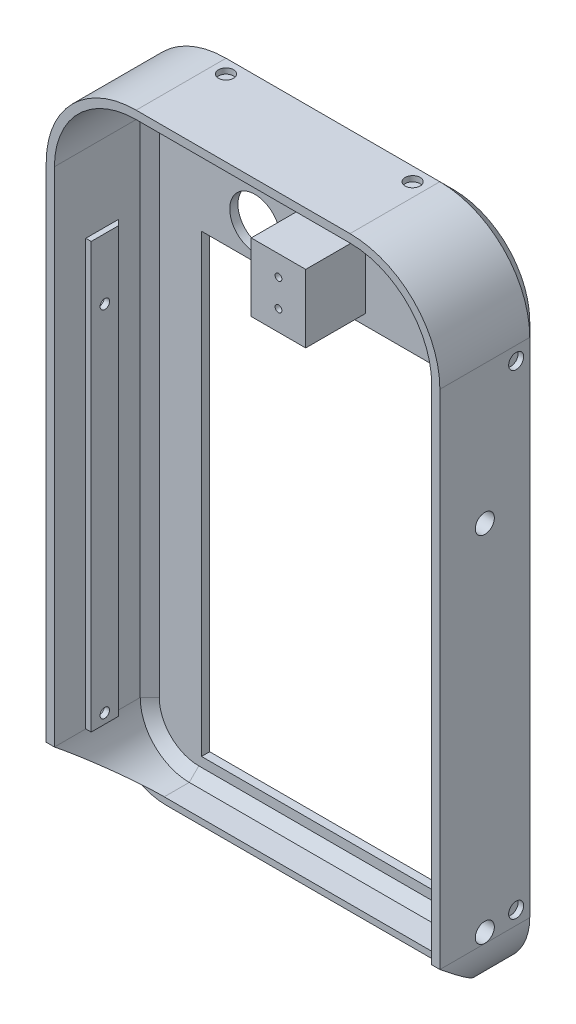
SolidWorks part; units mm, degrees
ref_plane "Plan de face" through (0, 0, 0) normal (0, 0, 1) x (1, 0, 0)
ref_plane "Plan de dessus" through (0, 0, 0) normal (0, 1, 0) x (1, 0, 0)
ref_plane "Plan de droite" through (0, 0, 0) normal (1, 0, 0) x (0, 0, -1)
sketch "Esquisse1" plane through (0, 0, 0) normal (0, 0, 1) x (1, 0, 0)
  line L1 (-12.2348, 13.2576) -> (7.7652, 13.2576)
  line L2 (-12.2348, 13.2576) -> (-12.2348, -11.7424)
  line L3 (-12.2348, -11.7424) -> (7.7652, -11.7424)
  line L4 (7.7652, 13.2576) -> (7.7652, -11.7424)
  dimension "D1" = 20
  dimension "D2" = 25
extrude "Boss.-Extru.1" add sketch "Esquisse1" along normal blind 22
sketch "Esquisse2" plane through (0, 0, 22) normal (0, 0, 1) x (1, 0, 0)
  line L0 (-12.2348, 0.7576) -> (7.7652, 0.7576) construction
  line L1 (-12.2348, 13.2576) -> (-12.2348, -11.7424) construction
  line L2 (7.7652, -11.7424) -> (7.7652, 13.2576) construction
  line L3 (-2.2348, 5.7576) -> (-2.2348, -4.2424) construction
  circle A0 centre (-2.2348, 5.7576) radius 1.25
  circle A1 centre (-2.2348, -4.2424) radius 1.25
  point P13 (-2.2348, 0.7576)
  point P14 (-2.2348, 0.7576)
  dimension "D2" = 2.5
  dimension "D1" = 10
extrude "Enlèv. mat.-Extru.1" cut sketch "Esquisse2" against normal blind 15
sketch "Esquisse3" plane through (0, 0, 0) normal (0, 0, -1) x (-1, 0, 0)
  line L1 (74.4938, -15.7424) -> (-70.0241, -15.7424)
  line L2 (74.4938, -15.7424) -> (74.4938, 45.7576)
  line L3 (74.4938, 45.7576) -> (-70.0241, 45.7576)
  line L4 (-70.0241, -15.7424) -> (-70.0241, 45.7576)
  line L5 (-7.7652, 13.2576) -> (12.2348, 13.2576) construction
  line L7 (12.2348, -11.7424) -> (-7.7652, -11.7424) construction
  line L8 (12.2348, 13.2576) -> (12.2348, -11.7424) construction
  line L9 (-7.7652, -11.7424) -> (-7.7652, 13.2576) construction
  dimension "D1" = 4
  dimension "D2" = 62.2589
  dimension "D3" = 62.2589
  dimension "D4" = 32.5
extrude "Wall" add sketch "Esquisse3" along normal blind 3
sketch "Esquisse4" plane through (0, 0, -3) normal (0, 0, -1) x (-1, 0, 0)
  line L1 (-70.0241, -15.7424) -> (74.4938, -15.7424) construction
  line L2 (12.2348, 13.2576) -> (12.2348, -11.7424) construction
  line L3 (-32.7652, 28.7576) -> (32.2348, 28.7576) construction
  line L4 (-32.7652, 39.2576) -> (32.2348, 39.2576)
  line L5 (-32.7652, 18.2576) -> (32.2348, 18.2576)
  line L7 (74.4938, -15.7424) -> (74.4938, 45.7576) construction
  circle A0 centre (32.8698, -3.4521) radius 9.25
  arc A1 (-32.7652, 39.2576) -> (-32.7652, 18.2576) centre (-32.7652, 28.7576) ccw
  arc A2 (32.2348, 18.2576) -> (32.2348, 39.2576) centre (32.2348, 28.7576) ccw
  point P8 (-0.2652, 28.7576)
  point P13 (1.2337, 22.3958)
  point P14 (-29.4209, 22.6205)
  point P17 (-32.7652, 17.5685)
  dimension "D1" = 18.5
  dimension "D7" = 10.5
  dimension "D2" = 20.635
  dimension "D3" = 12.2903
  dimension "D4" = 44.5
  dimension "D5" = 42.2589
  dimension "D6" = 65
extrude "Cameras" cut sketch "Esquisse4" against normal up to next
sketch "Esquisse9" plane through (0, 0, -3) normal (0, 0, -1) x (-1, 0, 0)
  line L0 (-48.0241, -182.7424) -> (52.4938, -182.7424)
  line L1 (-70.0241, -15.7424) -> (-48.0241, -15.7424)
  line L2 (-70.0241, -15.7424) -> (-70.0241, -192.7424)
  line L4 (-48.0241, -15.7424) -> (-48.0241, -182.7424)
  line L5 (74.4938, -15.7424) -> (52.4938, -15.7424)
  line L6 (74.4938, -15.7424) -> (74.4938, -192.7424)
  line L8 (52.4938, -15.7424) -> (52.4938, -182.7424)
  line L9 (-70.0241, -192.7424) -> (74.4938, -192.7424)
  dimension "D1" = 22
  dimension "D2" = 22
  dimension "D3" = 167
  dimension "D4" = 10
extrude "Screen" add sketch "Esquisse9" against normal up to surface (3 mm away) up to face at (-42.1198, -3.4521, 0)
sketch "Esquisse5" plane through (0, 0, 0) normal (0, 0, 1) x (1, 0, 0)
  line L2 (-74.4938, -192.7424) -> (-74.4938, 45.7576)
  line L7 (70.0241, 45.7576) -> (70.0241, -192.7424)
  line L10 (-74.4938, 45.7576) -> (70.0241, 45.7576) construction
  line L11 (-74.4938, 45.7576) -> (70.0241, 45.7576)
  line L12 (-71.4938, -189.7424) -> (-71.4938, 42.7576)
  line L13 (-71.4938, 42.7576) -> (67.0241, 42.7576)
  line L14 (67.0241, 42.7576) -> (67.0241, -189.7424)
  line L15 (-2.2348, 42.7576) -> (-2.2348, 45.7576) construction
  line L18 (-74.4938, -192.7424) -> (70.0241, -192.7424) construction
  line L19 (-71.4938, -189.7424) -> (67.0241, -189.7424)
  line L20 (-2.2348, -189.7424) -> (-2.2348, -192.7424) construction
  line L21 (-71.4938, -189.7424) -> (-74.4938, -189.7424) construction
  point P17 (-71.4938, -189.7424)
  point P18 (61.5641, -189.7424)
  line M11 (-74.4938, 45.7576) -> (-74.4938, -192.7424)
  line M13 (70.0241, -192.7424) -> (70.0241, 45.7576)
  line M14 (70.0241, 45.7576) -> (-74.4938, 45.7576)
  line M32 (-74.4938, -192.7424) -> (70.0241, -192.7424)
  dimension "D1" = 3
extrude "Boss.-Extru.3" add sketch "Esquisse5" along normal blind 35 contours L19 L12 L13 L14 M14 M11 M32 M13 region at (-71.7051, -73.4924, 0)
fillet "Congé1" radius 30 2 edges at (-71.4938, 42.7576, 17.5) (67.0241, 42.7576, 17.5)
fillet "Congé2" radius 33 2 edges at (-74.4938, 45.7576, 16) (70.0241, 45.7576, 16)
fillet "Congé3" radius 18 2 edges at (-71.4938, -189.7424, 17.5) (67.0241, -189.7424, 17.5)
fillet "Congé4" radius 21 2 edges at (-74.4938, -192.7424, 16) (70.0241, -192.7424, 16)
chamfer "Chanfrein1" distance 5 angle 45 8 edges at (-74.4938, -79.4924, -3) (-64.8283, 36.0921, -3) (-2.2348, 45.7576, -3) (70.0241, -79.4924, -3) (60.3586, 36.0921, -3) (-68.343, -186.5917, -3) (-2.2348, -192.7424, -3) (63.8733, -186.5917, -3)
chamfer "Chanfrein2" distance 3.5 angle 45 8 edges at (-71.4938, -79.4924, 0) (-62.707, 33.9708, 0) (67.0241, -79.4924, 0) (-2.2348, 42.7576, 0) (58.2373, 33.9708, 0) (-66.2217, -184.4703, 0) (-2.2348, -189.7424, 0) (61.752, -184.4703, 0)
sketch "Esquisse16" plane through (70.0241, 0, 0) normal (1, 0, 0) x (0, 0, -1)
  line L0 (-35, -171.7424) -> (-12, -190.286)
  line L1 (-12, -190.286) -> (-12, -192.7424)
  line L2 (-12, -192.7424) -> (-35, -192.7424)
  line L3 (-35, -192.7424) -> (-35, -171.7424)
  line L4 (-2, -192.7424) -> (-2, -171.7424) construction
  line L5 (-35, -192.7424) -> (-2, -192.7424) construction
  dimension "D1" = 10
extrude "Enlèv. mat.-Extru.9" cut sketch "Esquisse16" against normal through all
ref_plane "Plan1" through (0, 0, 13.5) normal (0, 0, 1) x (1, 0, 0)
sketch "Esquisse11" plane through (0, 0, 13.5) normal (0, 0, 1) x (1, 0, 0)
  line L0 (67.0241, 12.7576) -> (67.0241, -171.7424) construction
  line L1 (67.0241, -171.7424) -> (59.5641, -171.7424)
  line L2 (67.0241, -171.7424) -> (67.0241, -15.7424)
  line L3 (67.0241, -15.7424) -> (59.5641, -15.7424)
  line L4 (59.5641, -171.7424) -> (59.5641, -15.7424)
  line L5 (-69.4938, -171.7424) -> (-71.4938, -171.7424)
  line L6 (-69.4938, -171.7424) -> (-69.4938, -15.7424)
  line L7 (-69.4938, -15.7424) -> (-71.4938, -15.7424)
  line L8 (-71.4938, -171.7424) -> (-71.4938, -15.7424)
  line L10 (-71.4938, -171.7424) -> (-71.4938, 12.7576) construction
  point P10 (61.5641, -180.8212)
  point P16 (0, 0)
  dimension "D1" = 7.46
  dimension "D2" = 2
extrude "Boss.-Extru.5" add sketch "Esquisse11" along normal blind 10
chamfer "Chanfrein3" distance 2 angle 45 1 edges at (-71.4938, -93.7424, 13.5)
chamfer "Chanfrein4" distance 7.46 angle 45 1 edges at (67.0241, -93.7424, 13.5)
sketch "Esquisse12" plane through (59.5641, 0, 0) normal (-1, 0, 0) x (0, 0, 1)
  line L0 (23.5, -15.7424) -> (13.5, -15.7424) construction
  circle A0 centre (18.5, -38.1314) radius 1.75
  circle A1 centre (18.5, -168.1314) radius 1.75
  point P2 (0, 0)
  point P5 (18.5, -15.7424)
  dimension "D2" = 3.5
  dimension "D1" = 22.3889
  dimension "D3" = 130
extrude "Enlèv. mat.-Extru.5" cut sketch "Esquisse12" against normal through all both and the other way through all
sketch "Esquisse13" plane through (-74.4938, 0, 0) normal (-1, 0, 0) x (0, 0, 1)
  circle A0 centre (18.5, -38.1314) radius 3.5
  circle A1 centre (18.5, -168.1314) radius 3.5
  dimension "D1" = 7
extrude "Enlèv. mat.-Extru.6" cut sketch "Esquisse13" against normal blind 3
sketch "Esquisse14" plane through (70.0241, 0, 0) normal (1, 0, 0) x (0, 0, -1)
  circle A2 centre (-18.5, -168.1314) radius 3.5 construction
  circle A3 centre (-18.5, -38.1314) radius 3.5 construction
  circle A4 centre (-18.5, -168.1314) radius 3.5
  circle A5 centre (-18.5, -38.1314) radius 3.5
extrude "Enlèv. mat.-Extru.7" cut sketch "Esquisse14" against normal blind 8.46
sketch "Esquisse6" plane through (0, 45.7576, 0) normal (0, 1, 0) x (1, 0, 0)
  line L1 (37.0241, -35) -> (37.0241, -2) construction
  line L2 (32.0241, -7) -> (37.0241, -7) construction
  line L4 (-36.4938, -7) -> (-41.4938, -7) construction
  line L5 (-41.4938, -2) -> (-41.4938, -35) construction
  line L7 (37.0241, -2) -> (-41.4938, -2) construction
  circle A0 centre (32.0241, -7) radius 2.75
  circle A1 centre (-36.4938, -7) radius 2.75
  point P2 (26.5641, -6.2452)
  dimension "D2" = 5.5
  dimension "D1" = 5
  dimension "D3" = 5
extrude "Enlèv. mat.-Extru.2" cut sketch "Esquisse6" against normal blind 2
sketch "Esquisse7" plane through (70.0241, 0, 0) normal (1, 0, 0) x (0, 0, -1)
  line L0 (-2, 12.7576) -> (-35, 12.7576) construction
  line L2 (-2, -171.7424) -> (-2, 12.7576) construction
  line L3 (-7, -166.7424) -> (-7, -171.7424) construction
  line L5 (-7, 7.7576) -> (-7, 12.7576) construction
  line L6 (-2, 12.7576) -> (-35, 12.7576) construction
  line L7 (-35, -171.7424) -> (-2, -171.7424) construction
  circle A0 centre (-7, 7.7576) radius 2.75
  circle A1 centre (-7, -166.7424) radius 2.75
  point P4 (-7, -179.7424)
  dimension "D1" = 5.5
  dimension "D2" = 5
  dimension "D3" = 5
extrude "Enlèv. mat.-Extru.3" cut sketch "Esquisse7" against normal blind 2
sketch "Esquisse8" plane through (-74.4938, 0, 0) normal (-1, 0, 0) x (0, 0, 1)
  circle A2 centre (7, 7.7576) radius 2.75 construction
  circle A3 centre (7, -166.7424) radius 2.75 construction
  circle A4 centre (7, 7.7576) radius 2.75
  circle A5 centre (7, -166.7424) radius 2.75
extrude "Enlèv. mat.-Extru.4" cut sketch "Esquisse8" against normal blind 2
sketch "Esquisse15" plane through (0, -192.7424, 0) normal (0, -1, 0) x (1, 0, 0)
  circle A0 centre (-36.4938, 7) radius 2.75 construction
  circle A1 centre (32.0241, 7) radius 2.75 construction
  circle A2 centre (-36.4938, 7) radius 2.75
  circle A3 centre (32.0241, 7) radius 2.75
extrude "Enlèv. mat.-Extru.8" cut sketch "Esquisse15" against normal blind 2
